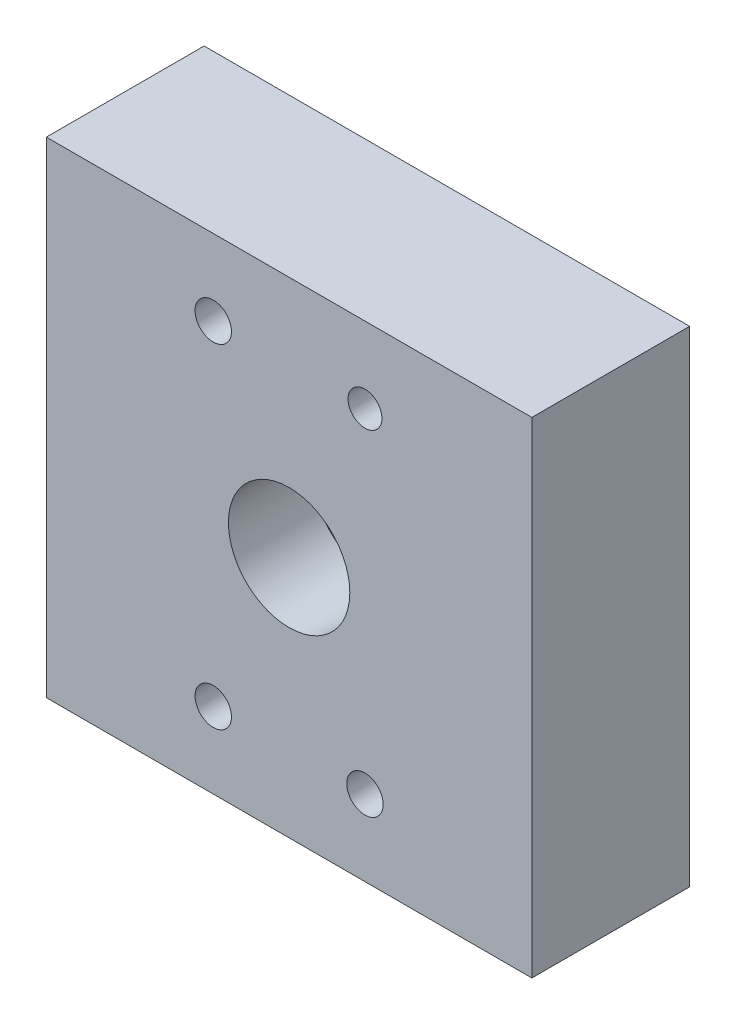
SolidWorks part; units mm, degrees
ref_plane "Front Plane" through (0, 0, 0) normal (1, 0, 0) x (0, 1, 0)
ref_plane "Top Plane" through (0, 0, 0) normal (0, 0, 1) x (0, 1, 0)
ref_plane "Right Plane" through (0, 0, 0) normal (0, 1, 0) x (-1, 0, 0)
sketch "Sketch1" plane through (0, 0, 0) normal (0, 0, 1) x (0, 1, 0)
  line L1 (-20, -20) -> (20, -20)
  line L2 (-20, -20) -> (-20, 20)
  line L3 (-20, 20) -> (20, 20)
  line L4 (20, -20) -> (20, 20)
  line L5 (-20, -20) -> (20, 20) construction
  line L6 (-20, 20) -> (20, -20) construction
  line L7 (-5, 5) -> (5, 5)
  line L8 (-5, 5) -> (-5, -5)
  line L9 (-5, -5) -> (5, -5)
  line L10 (5, 5) -> (5, -5)
  line L11 (-5, 5) -> (5, -5) construction
  line L12 (-5, -5) -> (5, 5) construction
  line L13 (5, -5) -> (-5, -5)
  line L14 (5, -5) -> (5, -13)
  line L15 (5, -13) -> (-5, -13)
  line L16 (-5, -5) -> (-5, -13)
  line L17 (-5, -13) -> (-8, -13)
  line L18 (-5, -13) -> (-5, -5)
  line L19 (-5, -5) -> (-8, -5)
  line L20 (-8, -13) -> (-8, -5)
  circle A0 centre (-10.5, 0) radius 0.9
  circle A1 centre (-10.5, 12.5) radius 0.9
  circle A2 centre (10.5, 0) radius 0.9
  circle A3 centre (10.5, 12.5) radius 0.9
  point P0 (0, 0)
  point P6 (0, 0)
  dimension "D4" = 8
  dimension "D1" = 40
  dimension "D2" = 40
  dimension "D3" = 10
  dimension "D5" = 3
extrude "Boss-Extrude1" add sketch "Sketch1" along normal blind 6 contours L1 L4 L3 L2 A2 A1 A0 L17 L20 L19 L8 L7 L10 L14 L15 A3 region at (0, -19.4343, 0)
sketch "Sketch11" plane through (0, 0, 6) normal (0, 0, 1) x (1, 0, 0)
  line L1 (-20, 20) -> (20, 20)
  line L2 (-20, 20) -> (-20, -20)
  line L3 (-20, -20) -> (20, -20)
  line L4 (20, 20) -> (20, -20)
  circle A0 centre (0, 0) radius 5
extrude "Boss-Extrude6" add sketch "Sketch11" along normal blind 7
sketch "Sketch13" plane through (0, 0, 0) normal (0, 0, -1) x (1, 0, 0)
  line L5 (-10, -17.5) -> (10, 17.5) construction
  line L6 (-10, 17.5) -> (10, -17.5) construction
  circle A0 centre (-6.25, 13.75) radius 1.5
  circle A1 centre (6.25, 13.75) radius 1.5
  circle A2 centre (6.25, -13.75) radius 1.5
  circle A3 centre (-6.25, -13.75) radius 1.5
  circle A4 centre (-6.25, 13.75) radius 3
  circle A5 centre (6.25, 13.75) radius 3
  circle A6 centre (-6.25, -13.75) radius 3
  circle A7 centre (6.25, -13.75) radius 1.3954
  circle A8 centre (6.25, -13.75) radius 3
  point P0 (0, 0)
  dimension "D1" = 20
  dimension "D2" = 35
  dimension "D3" = 2
  dimension "D4" = 2
extrude "Cut-Extrude5" cut sketch "Sketch13" against normal blind 27 contours A0 | A1 | A7 | A3 region at (-6.25, -13.75, 0) region at (6.25, -13.75, 0) region at (-6.25, 13.75, 0) region at (6.25, 13.75, 0)
extrude "Cut-Extrude6" cut sketch "Sketch13<3>" against normal blind 3 contours A6 A3 | A5 A1 | A4 A0 | A8 region at (-9.1651, -13.75, 0) region at (3.3349, -13.75, 0) region at (-9.1651, 13.75, 0)
sketch "Sketch13<3>" plane through (0, 0, 0) normal (0, 0, -1) x (1, 0, 0) same geometry as "Sketch13"
